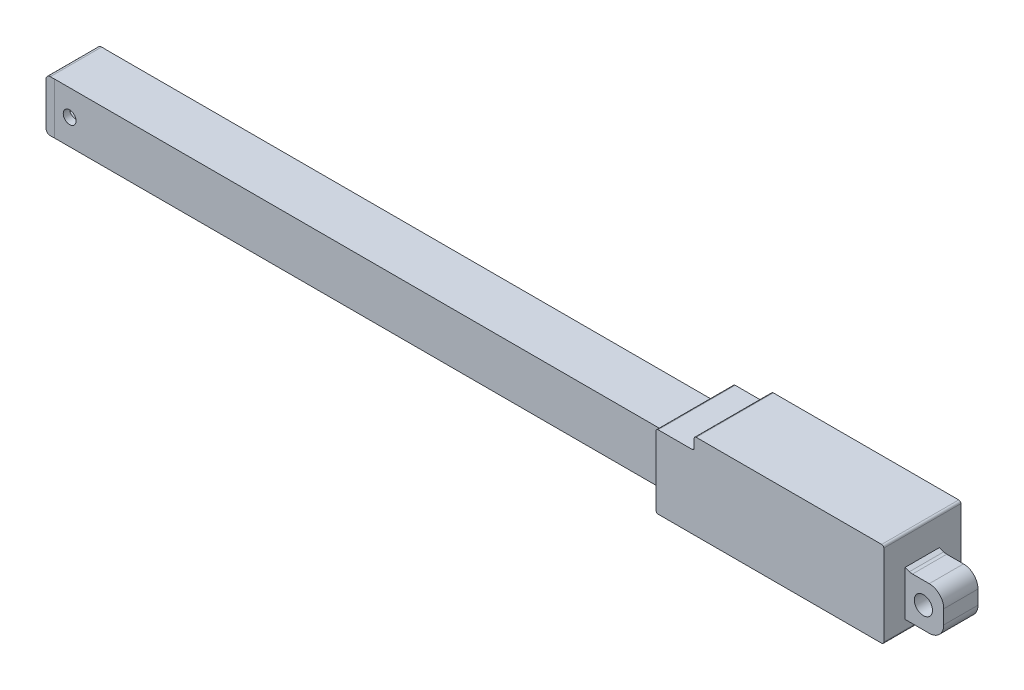
SolidWorks part; units mm, degrees
ref_plane "Front Plane" through (0, 0, 0) normal (0, 0, 1) x (1, 0, 0)
ref_plane "Top Plane" through (0, 0, 0) normal (0, 1, 0) x (1, 0, 0)
ref_plane "Right Plane" through (0, 0, 0) normal (1, 0, 0) x (0, 0, -1)
sketch "Sketch2" plane through (0, 0, 0) normal (0, 0, 1) x (1, 0, 0)
  line L0 (145.4775, 11.945) -> (145.4775, 14.0125)
  line L1 (1, 0) -> (145.4775, 0)
  line L2 (0, 1) -> (0, 10.945)
  line L3 (1, 11.945) -> (145.4775, 11.945)
  line L4 (145.4775, 0) -> (145.4775, 11.945)
  line L5 (145.4775, 0) -> (145.4775, -2.0675)
  line L6 (145.9775, -2.5675) -> (198.1775, -2.5675)
  line L7 (198.6775, 0) -> (198.6775, -2.0675)
  line L8 (198.1775, 17.4325) -> (154.8775, 17.4325)
  line L9 (154.3775, 16.9325) -> (154.3775, 15.0125)
  line L10 (153.8775, 14.5125) -> (145.9775, 14.5125)
  line L11 (198.6775, 0) -> (204.2883, 0)
  line L12 (207.6775, 3.3892) -> (207.6775, 6.6533)
  line L13 (204.2883, 10.0425) -> (200.3774, 10.0425)
  line L14 (199.6775, 10.169) -> (198.6775, 10.5425)
  line L15 (202.9275, 0) -> (202.9275, 10.0425) construction
  line L16 (2, 11.945) -> (2, 0)
  line L17 (198.6775, 10.5425) -> (198.6775, 16.9325)
  line L18 (2, 5.9725) -> (4, 5.9725) construction
  line L19 (0, 5.9725) -> (2, 5.9725) construction
  arc A0 (0, 10.945) -> (1, 11.945) centre (1, 10.945) cw
  arc A1 (1, 0) -> (0, 1) centre (1, 1) cw
  arc A2 (154.8775, 17.4325) -> (154.3775, 16.9325) centre (154.8775, 16.9325) ccw
  arc A3 (198.6775, 16.9325) -> (198.1775, 17.4325) centre (198.1775, 16.9325) ccw
  arc A4 (198.1775, -2.5675) -> (198.6775, -2.0675) centre (198.1775, -2.0675) ccw
  arc A5 (145.4775, -2.0675) -> (145.9775, -2.5675) centre (145.9775, -2.0675) ccw
  arc A6 (145.4775, 14.0125) -> (145.9775, 14.5125) centre (145.9775, 14.0125) cw
  arc A7 (154.3775, 15.0125) -> (153.8775, 14.5125) centre (153.8775, 15.0125) cw
  arc A8 (204.2883, 0) -> (207.6775, 3.3892) centre (204.2883, 3.3892) ccw
  arc A9 (207.6775, 6.6533) -> (204.2883, 10.0425) centre (204.2883, 6.6533) ccw
  circle A10 centre (202.9275, 5.0213) radius 2.125
  arc A11 (200.3774, 10.0425) -> (199.6775, 10.169) centre (200.3774, 12.0425) cw
  circle A12 centre (5.5, 5.9725) radius 1.5
  point P7 (0, 11.945)
  point P10 (0, 0)
  point P23 (191, -2.5)
  point P26 (145.4775, -2.5675)
  point P29 (145.4775, 14.5125)
  point P32 (154.3775, 14.5125)
  point P44 (202.9275, 5.0213)
  point P54 (4, 5.9725)
  dimension "D3" = 1
  dimension "D8" = 0.5
  dimension "D12" = 4.25
  dimension "D13" = 2
  dimension "D14" = 3
  dimension "D9" = 4.25
  dimension "D1" = 145.4775
  dimension "D2" = 11.945
  dimension "D4" = 53.2
  dimension "D5" = 17.08
  dimension "D6" = 20
  dimension "D7" = 44.3
  dimension "D10" = 10.0425
  dimension "D11" = 9
  dimension "D15" = 2
  dimension "D16" = 1
  dimension "D17" = 0.5
extrude "Boss-Extrude1" add sketch "Sketch2" along normal mid plane 18 contours L9 A7 L10 A6 L0 L4 L5 A5 L6 A4 A3 L8 A2 region at (174.5891, 7.0784, 0)
extrude "Boss-Extrude2" add sketch "Sketch2<3>" along normal mid plane 11.95 contours L3 L16 L1 L4 A12 region at (74.0214, 5.9725, 0)
sketch "Sketch2<3>" plane through (0, 0, 0) normal (0, 0, 1) x (1, 0, 0) same geometry as "Sketch2"
extrude "Boss-Extrude3" add sketch "Sketch2<4>" along normal mid plane 12 contours A1 L1 L16 L3 A0 L2 region at (1.0142, 5.9725, 0)
sketch "Sketch2<4>" plane through (0, 0, 0) normal (0, 0, 1) x (1, 0, 0) same geometry as "Sketch2"
sketch "Sketch7" plane through (0, 0, 0) normal (-1, 0, 0) x (0, 0, 1)
  line L0 (0, 1) -> (6, 5.9725) construction
  line L1 (6, 1) -> (-6, 1) construction
  line L2 (6, 1) -> (6, 10.945) construction
  line L3 (6, 5.9725) -> (0, 5.9725) construction
  circle A0 centre (0, 5.9725) radius 4.45
  dimension "D1" = 8.9
extrude "Cut-Extrude4" cut sketch "Sketch7" against normal blind 138
sketch "Sketch8" plane through (0, 0, 9) normal (0, 0, 1) x (1, 0, 0)
  line L0 (198.6775, 10.5425) -> (211.4521, 15.9059)
  line L1 (211.4521, 15.9059) -> (207.0125, -2.0597)
  line L2 (207.0125, -2.0597) -> (198.6775, 0)
  line L3 (198.6775, 0) -> (204.2883, 0) construction
  line L4 (198.6775, 0) -> (198.6775, 10.5425)
extrude "Cut-Extrude6" cut sketch "Sketch8" against normal mid plane 10
sketch "Sketch10" plane through (0, 0, -9) normal (0, 0, -1) x (-1, 0, 0)
  line L0 (-198.6775, 10.5425) -> (-218.6867, 39.1128)
  line L1 (-218.6867, 39.1128) -> (-201.4433, -35.5929)
  line L2 (-201.4433, -35.5929) -> (-198.6775, 0)
  line L3 (-198.6775, 0) -> (-198.6775, 10.5425)
extrude "Cut-Extrude7" cut sketch "Sketch10" against normal mid plane 10
